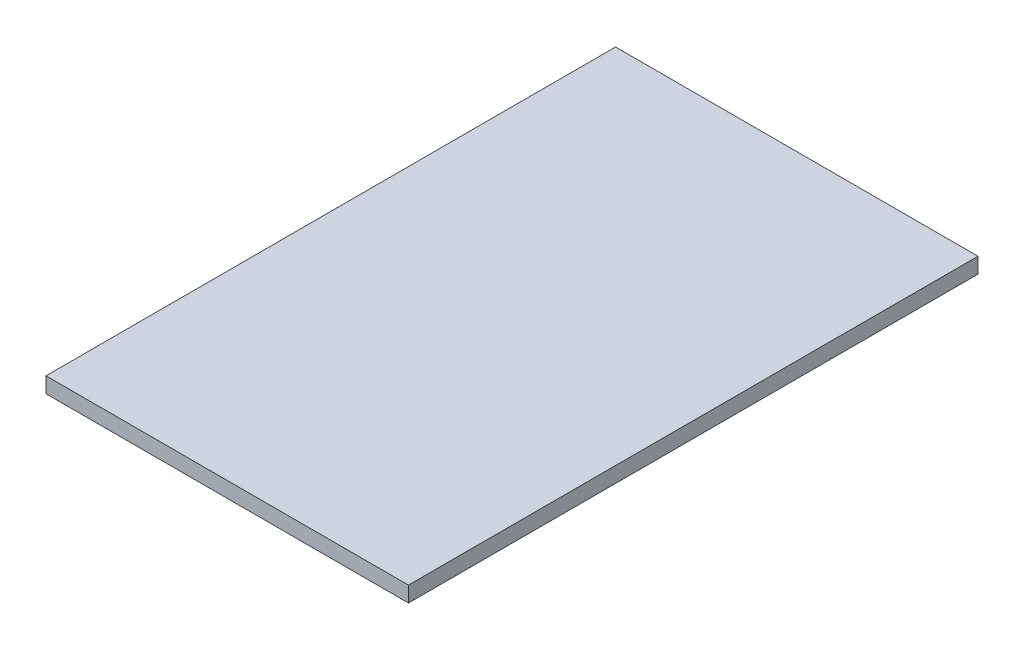
SolidWorks part; units mm, degrees
ref_plane "Front Plane" through (0, 0, 0) normal (0, 0, 1) x (1, 0, 0)
ref_plane "Top Plane" through (0, 0, 0) normal (0, 1, 0) x (1, 0, 0)
ref_plane "Right Plane" through (0, 0, 0) normal (1, 0, 0) x (0, 0, -1)
sketch "Sketch1" plane through (0, 0, 0) normal (0, 1, 0) x (1, 0, 0)
  line L1 (-889, -1397) -> (889, -1397)
  line L2 (-889, -1397) -> (-889, 1397)
  line L3 (-889, 1397) -> (889, 1397)
  line L4 (889, -1397) -> (889, 1397)
  line L5 (-889, -1397) -> (889, 1397) construction
  line L6 (-889, 1397) -> (889, -1397) construction
  point P0 (0, 0)
  dimension "D1" = 2794
  dimension "D2" = 1778
extrude "Boss-Extrude1" add sketch "Sketch1" along normal blind 76.2
sketch "Sketch6" plane through (0, 0, 0) normal (0, -1, 0) x (1, 0, 0)
  line L0 (152.7624, 1397) -> (152.7624, -1397) construction
  line L2 (889, -1397) -> (-889, -1397) construction
  line L3 (-889, 1397) -> (889, 1397) construction
  text T0 "<b>\"You're a young man of great...</b>\r\n<b>cannons when we were still downtown\"</b>\r\n<b>-Washington, Right Hand Man</b>" font "Century Gothic" height 101.6
extrude "Cut-Extrude2" cut sketch "Sketch6" against normal blind 38.1
